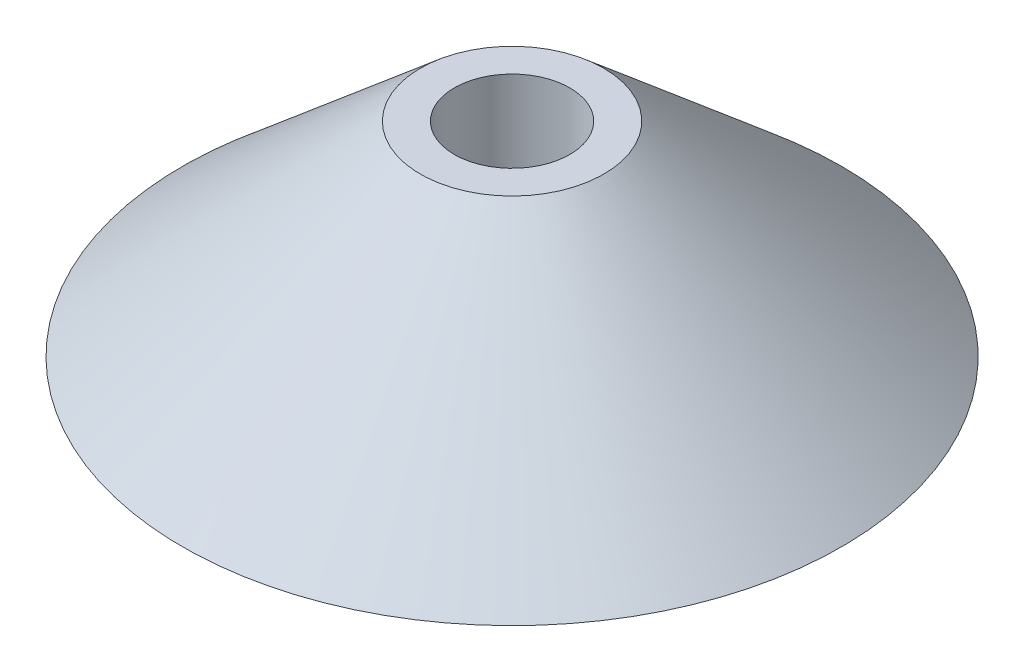
SolidWorks part; units mm, degrees
ref_plane "Ebene vorne" through (0, 0, 0) normal (0, 0, 1) x (1, 0, 0)
ref_plane "Ebene oben" through (0, 0, 0) normal (0, 1, 0) x (1, 0, 0)
ref_plane "Ebene rechts" through (0, 0, 0) normal (1, 0, 0) x (0, 0, -1)
sketch "Sketch1" plane through (0, 0, 0) normal (0, 0, 1) x (1, 0, 0)
  line L0 (0, 11.3265) -> (0, -9.4898) construction
  line L2 (-2.7, 6) -> (-9.7, 0)
  line L3 (-9.7, 0) -> (-1.7, 0)
  line L4 (-2.7, 6) -> (-1.7, 6)
  line L5 (-1.7, 6) -> (-1.7, 0)
  point P5 (-1.431, 0)
  dimension "D1" = 6
  dimension "D2" = 1
  dimension "D3" = 3.4
  dimension "D4" = 8
revolve "Revolve1" add sketch "Sketch1" angle 360 about L0
